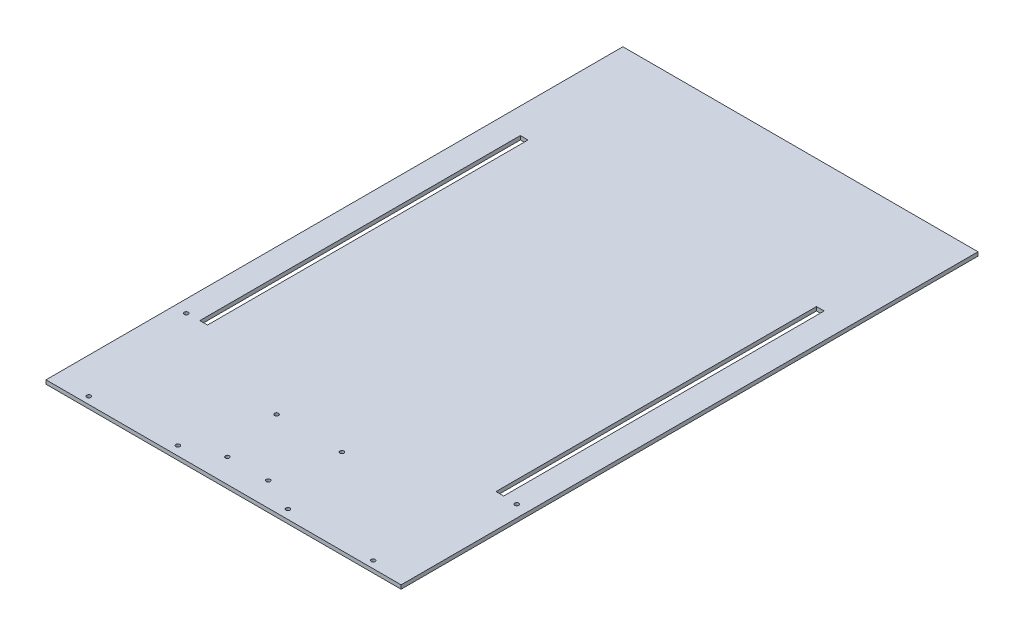
SolidWorks part; units mm, degrees
ref_plane "Front Plane" through (0, 0, 0) normal (0, 0, 1) x (1, 0, 0)
ref_plane "Top Plane" through (0, 0, 0) normal (0, 1, 0) x (1, 0, 0)
ref_plane "Right Plane" through (0, 0, 0) normal (1, 0, 0) x (0, 0, -1)
sketch "Sketch1" plane through (0, 0, 0) normal (0, 0, 1) x (1, 0, 0)
  line L1 (19.86, -14.9279) -> (-257.14, -14.9279)
  line L2 (19.86, -14.9279) -> (19.86, -11.9279)
  line L3 (19.86, -11.9279) -> (-257.14, -11.9279)
  line L4 (-257.14, -14.9279) -> (-257.14, -11.9279)
  line L5 (19.86, -14.9279) -> (-257.14, -11.9279) construction
  line L6 (19.86, -11.9279) -> (-257.14, -14.9279) construction
  point P0 (-118.64, -13.4279)
extrude "Boss-Extrude1" add sketch "Sketch1" along normal blind 450
sketch "Sketch2" plane through (0, -11.9279, 0) normal (0, 1, 0) x (1, 0, 0)
  line L0 (19.86, -450) -> (-257.14, -450) construction
  line L1 (-237.14, -100) -> (-231.14, -100)
  line L2 (-237.14, -100) -> (-237.14, -350)
  line L3 (-237.14, -350) -> (-231.14, -350)
  line L4 (-231.14, -100) -> (-231.14, -350)
  line L5 (-6.14, -100) -> (-0.14, -100)
  line L6 (-6.14, -100) -> (-6.14, -350)
  line L7 (-6.14, -350) -> (-0.14, -350)
  line L8 (-0.14, -100) -> (-0.14, -350)
  line L9 (19.86, 0) -> (-257.14, 0) construction
  line L10 (-257.14, -450) -> (-257.14, 0) construction
  line L11 (19.86, -450) -> (19.86, 0) construction
  dimension "D1" = 100
  dimension "D2" = 100
  dimension "D3" = 100
  dimension "D4" = 100
  dimension "D5" = 20
  dimension "D6" = 20
  dimension "D7" = 6
  dimension "D8" = 6
extrude "Cut-Extrude1" cut sketch "Sketch2" against normal up to next
sketch "Sketch3" plane through (0, -11.9279, 0) normal (0, 1, 0) x (1, 0, 0)
  circle A0 centre (-102.46, -431.323) radius 1.55
  circle A1 centre (-75.46, -442.9832) radius 1.55
  circle A2 centre (-92.91, -383.4048) radius 1.55
  circle A3 centre (10.54, -350.4048) radius 1.55
  circle A4 centre (-7.46, -444.4332) radius 1.55
  circle A5 centre (-247.34, -350.4056) radius 1.55
  circle A6 centre (-229.34, -444.434) radius 1.55
  circle A7 centre (-161.34, -442.984) radius 1.55
  circle A8 centre (-134.34, -431.3238) radius 1.55
  circle A9 centre (-143.89, -383.4056) radius 1.55
extrude "Cut-Extrude2" cut sketch "Sketch3" against normal up to next
